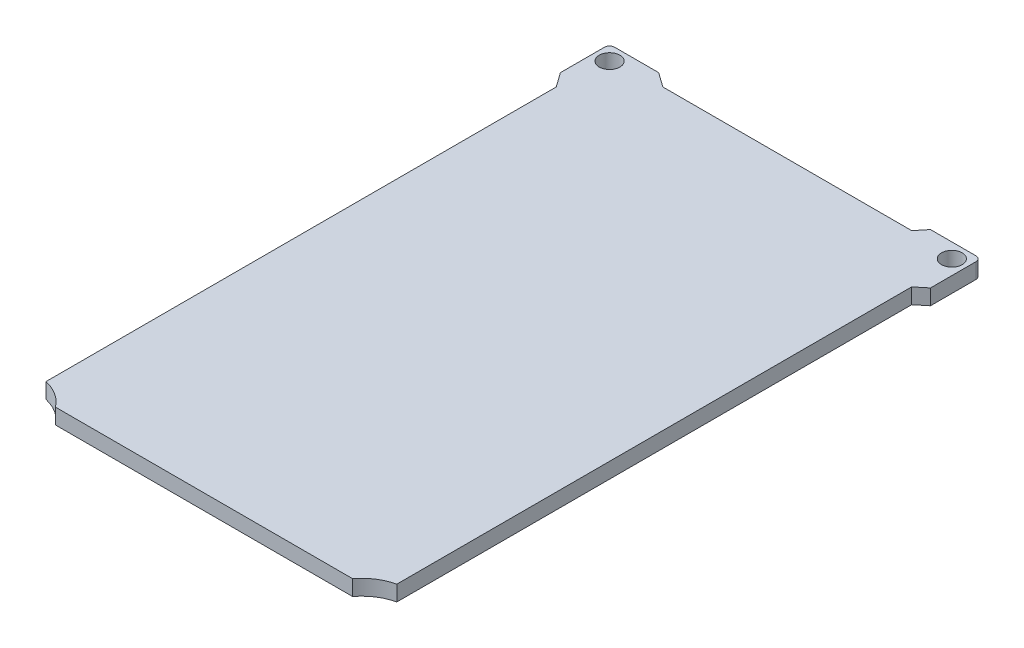
SolidWorks part; units mm, degrees
ref_plane "Front Plane" through (0, 0, 0) normal (0, 0, 1) x (1, 0, 0)
ref_plane "Top Plane" through (0, 0, 0) normal (0, 1, 0) x (1, 0, 0)
ref_plane "Right Plane" through (0, 0, 0) normal (1, 0, 0) x (0, 0, -1)
sketch "Sketch1" plane through (0, 0, 0) normal (0, 1, 0) x (1, 0, 0)
  line L1 (20, -32) -> (-20, -32)
  line L2 (20, -32) -> (20, 32)
  line L3 (20, 32) -> (-20, 32)
  line L4 (-20, -32) -> (-20, 32)
  line L5 (20, -32) -> (-20, 32) construction
  line L6 (20, 32) -> (-20, -32) construction
  line L7 (18, -30) -> (-18, -30)
  line L8 (18, -30) -> (18, 30)
  line L9 (18, 30) -> (-18, 30)
  line L10 (-18, -30) -> (-18, 30)
  line L11 (18, -30) -> (-18, 30) construction
  line L12 (18, 30) -> (-18, -30) construction
  point P0 (0, 0)
  point P6 (0, 0)
  dimension "D1" = 40
  dimension "D2" = 64
  dimension "D3" = 2
  dimension "D4" = 2
extrude "Boss-Extrude1" add sketch "Sketch1" along normal blind 1.5 contours L10 L7 L8 L9 region at (0, 0, 0)
sketch "Sketch5" plane through (0, 1.5, 0) normal (0, 1, 0) x (1, 0, 0)
  line L0 (-18, -30) -> (-18, 30) construction
  line L1 (18, 30) -> (-18, 30) construction
  line L2 (0, 30) -> (0, -30) construction
  line L3 (18, -30) -> (-18, -30) construction
  line L4 (-18, 25.5) -> (-18, 30)
  line L5 (18, -30) -> (18, 30) construction
  line L6 (18, 0) -> (-18, 0) construction
  line L7 (-18, 30) -> (-13.5, 30)
  line L8 (18, 30) -> (13.5, 30)
  line L9 (18, 25.5) -> (18, 30)
  line L10 (18, -25.5) -> (18, -30)
  line L11 (18, -30) -> (13.5, -30)
  line L12 (-18, -30) -> (-13.5, -30)
  line L13 (-18, -25.5) -> (-18, -30)
  arc A0 (-18, 25.5) -> (-13.5, 30) centre (-18, 30) ccw
  arc A1 (18, 25.5) -> (13.5, 30) centre (18, 30) cw
  arc A2 (18, -25.5) -> (13.5, -30) centre (18, -30) ccw
  arc A3 (-18, -25.5) -> (-13.5, -30) centre (-18, -30) cw
  point P25 (0, 0)
  line M4 (-18, 30) -> (-18, -30)
  line M5 (-18, -30) -> (18, -30)
  line M6 (18, -30) -> (18, 30)
  line M7 (18, 30) -> (-18, 30)
  dimension "D2" = 4.5
  dimension "D1" = 4.5
  dimension "D3" = 13.5
  dimension "D4" = 25.5
extrude "Cut-Extrude2" cut sketch "Sketch5" against normal blind 1.5 contours A2 M6 M5 | A3 M4 M5 region at (16.0901, 1.5, 28.0901) region at (-16.0901, 1.5, 28.0901)
sketch "Sketch6" plane through (0, 1.5, 0) normal (0, 1, 0) x (1, 0, 0)
  line L0 (-18, -25.5) -> (-18, 30) construction
  line L1 (17, -29) -> (-17, -29)
  line L2 (17, -29) -> (17, 29)
  line L3 (17, 29) -> (-17, 29)
  line L4 (-17, -29) -> (-17, 29)
  line L5 (17, -29) -> (-17, 29) construction
  line L6 (17, 29) -> (-17, -29) construction
  line L7 (18, 30) -> (-18, 30) construction
  point P0 (0, 0)
  dimension "D1" = 1
  dimension "D2" = 1
extrude "Cut-Extrude3" cut sketch "Sketch6" against normal blind 1.5 flip side to cut
sketch "Sketch7" plane through (0, 1.5, 0) normal (0, 1, 0) x (1, 0, 0)
  line L0 (0, -29) -> (0, -15.533) construction
  line L1 (-22.5, -29) -> (22.5, -29)
  line L2 (-22.5, -29) -> (-22.5, -27.3)
  line L3 (-22.5, -27.3) -> (22.5, -27.3)
  line L4 (22.5, -29) -> (22.5, -27.3)
  line L5 (-22.5, -29) -> (22.5, -27.3) construction
  line L6 (-22.5, -27.3) -> (22.5, -29) construction
  line L7 (-13.6125, -29) -> (13.6125, -29) construction
  point P4 (0, -28.15)
  dimension "D1" = 45
  dimension "D2" = 1.7
  dimension "D3" = 0
extrude "Cut-Extrude4" cut sketch "Sketch7" against normal blind 10
extrude "Boss-Extrude2" add sketch "Sketch5<3>" against normal blind 1.5 contours A1 M6 M7 | A0 M4 M7 region at (16.0901, 1.5, -28.0901) region at (-16.0901, 1.5, -28.0901)
sketch "Sketch5<3>" plane through (0, 1.5, 0) normal (0, 1, 0) x (1, 0, 0) same geometry as "Sketch5"
chamfer "Chamfer1" distance 2 angle 45 4 edges at (-13.6125, 0.75, -29) (-17, 0.75, -25.6125) (13.6125, 0.75, -29) (17, 0.75, -25.6125) first distance on face at (0, 0.75, -29) first distance on face at (-17, 0.75, 0) first distance on face at (13.5422, 0.75, -29.4984) first distance on face at (17.4984, 0.75, -25.5422)
fillet "Fillet1" radius 0.5 2 edges at (18, 0.75, -30) (-18, 0.75, -30)
sketch "Sketch8" plane through (0, 1.5, 0) normal (0, 1, 0) x (1, 0, 0)
  line L0 (12.2816, 29) -> (-11.8348, 29) construction
  line L1 (18, 25.1011) -> (18, 29.5) construction
  line L3 (-18, 29.5) -> (-18, 25.24) construction
  line L4 (-13.24, 30) -> (-17.5, 30) construction
  line L5 (17.5, 30) -> (13.1011, 30) construction
  circle A0 centre (-16.5858, 28.5858) radius 1
  circle A1 centre (16.5858, 28.5858) radius 1
  point P2 (-16.6581, 28.7858)
  point P5 (0, 0)
  point P6 (0.2234, 29)
  point P7 (16.5134, 28.7858)
  point P10 (-16.5858, 28.7858)
  point P11 (16.5858, 28.7858)
  point P12 (0, 0)
  point P14 (16.5858, 28.5858)
  point P18 (-16.5858, 28.5858)
  point P20 (-15.8538, 30)
  point P21 (-15.7076, 30)
  dimension "D3" = 2
  dimension "D1" = 1.4142
  dimension "D2" = 1.4142
  dimension "D4" = 1.4142
  dimension "D5" = 1.4142
extrude "Cut-Extrude5" cut sketch "Sketch8" against normal blind 10
